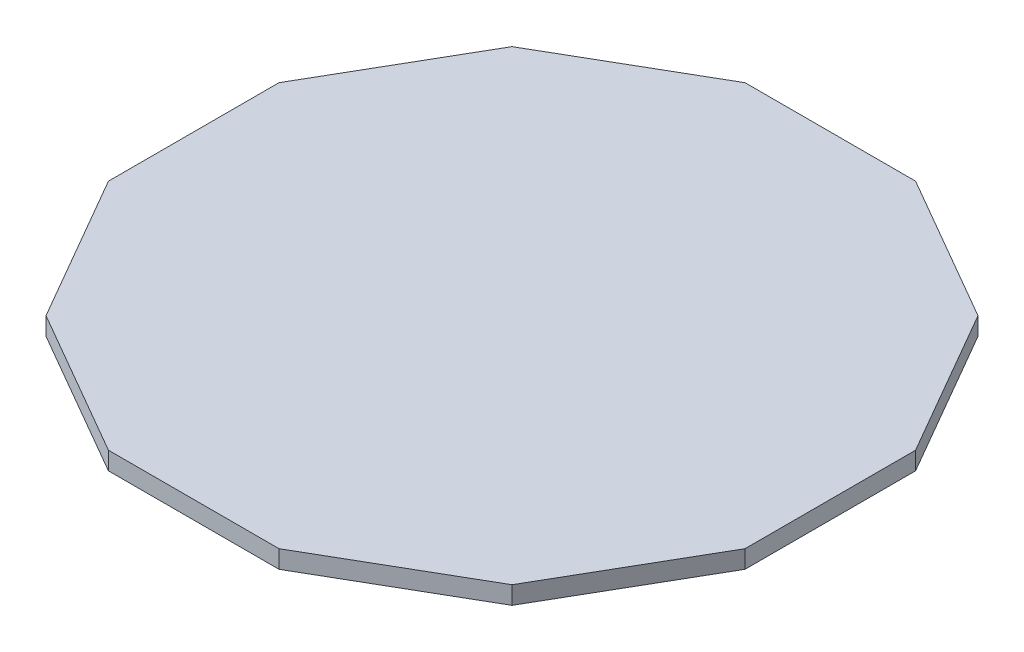
SolidWorks part; units mm, degrees
ref_plane "Front Plane" through (0, 0, 0) normal (0, 0, 1) x (1, 0, 0)
ref_plane "Top Plane" through (0, 0, 0) normal (0, 1, 0) x (1, 0, 0)
ref_plane "Right Plane" through (0, 0, 0) normal (1, 0, 0) x (0, 0, -1)
sketch "Sketch1" plane through (0, 0, 0) normal (0, 1, 0) x (1, 0, 0)
  line L0 (13.148, 49.069) -> (-13.148, 49.069)
  line L1 (-13.148, 49.069) -> (-35.921, 35.921)
  line L2 (-35.921, 35.921) -> (-49.069, 13.148)
  line L3 (-49.069, 13.148) -> (-49.069, -13.148)
  line L4 (-49.069, -13.148) -> (-35.921, -35.921)
  line L5 (-35.921, -35.921) -> (-13.148, -49.069)
  line L6 (-13.148, -49.069) -> (13.148, -49.069)
  line L7 (13.148, -49.069) -> (35.921, -35.921)
  line L8 (35.921, -35.921) -> (49.069, -13.148)
  line L9 (49.069, -13.148) -> (49.069, 13.148)
  line L10 (49.069, 13.148) -> (35.921, 35.921)
  line L11 (35.921, 35.921) -> (13.148, 49.069)
  circle A0 centre (0, 0) radius 50.8
  dimension "D1" = 101.6
extrude "Boss-Extrude1" add sketch "Sketch1" against normal blind 2.921 contours L10 L11 L0 L1 L2 L3 L4 L5 L6 L7 L8 L9 region at (0, 0, 0)
sketch "Sketch2" plane through (0, 0, 0) normal (0, 1, 0) x (1, 0, 0)
  line L24 (51.99, 13.9307) -> (38.0593, 38.0593)
  line L25 (38.0593, 38.0593) -> (13.9307, 51.99)
  line L26 (13.9307, 51.99) -> (-13.9307, 51.99)
  line L27 (-13.9307, 51.99) -> (-38.0593, 38.0593)
  line L28 (-38.0593, 38.0593) -> (-51.99, 13.9307)
  line L29 (-51.99, 13.9307) -> (-51.99, -13.9307)
  line L30 (-51.99, -13.9307) -> (-38.0593, -38.0593)
  line L31 (-38.0593, -38.0593) -> (-13.9307, -51.99)
  line L32 (-13.9307, -51.99) -> (13.9307, -51.99)
  line L33 (13.9307, -51.99) -> (38.0593, -38.0593)
  line L34 (38.0593, -38.0593) -> (51.99, -13.9307)
  line L35 (51.99, -13.9307) -> (51.99, 13.9307)
  line L36 (51.99, 13.9307) -> (38.0593, 38.0593)
  line L37 (38.0593, 38.0593) -> (13.9307, 51.99)
  line L38 (13.9307, 51.99) -> (-13.9307, 51.99)
  line L39 (-13.9307, 51.99) -> (-38.0593, 38.0593)
  line L40 (-38.0593, 38.0593) -> (-51.99, 13.9307)
  line L41 (-51.99, 13.9307) -> (-51.99, -13.9307)
  line L42 (-51.99, -13.9307) -> (-38.0593, -38.0593)
  line L43 (-38.0593, -38.0593) -> (-13.9307, -51.99)
  line L44 (-13.9307, -51.99) -> (13.9307, -51.99)
  line L45 (13.9307, -51.99) -> (38.0593, -38.0593)
  line L46 (38.0593, -38.0593) -> (51.99, -13.9307)
  line L47 (51.99, -13.9307) -> (51.99, 13.9307)
  line L60 (49.069, 13.148) -> (35.921, 35.921)
  line L61 (35.921, 35.921) -> (13.148, 49.069)
  line L62 (13.148, 49.069) -> (-13.148, 49.069)
  line L63 (-13.148, 49.069) -> (-35.921, 35.921)
  line L64 (-35.921, 35.921) -> (-49.069, 13.148)
  line L65 (-49.069, 13.148) -> (-49.069, -13.148)
  line L66 (-49.069, -13.148) -> (-35.921, -35.921)
  line L67 (-35.921, -35.921) -> (-13.148, -49.069)
  line L68 (-13.148, -49.069) -> (13.148, -49.069)
  line L69 (13.148, -49.069) -> (35.921, -35.921)
  line L70 (35.921, -35.921) -> (49.069, -13.148)
  line L71 (49.069, -13.148) -> (49.069, 13.148)
  line L72 (49.069, 13.148) -> (35.921, 35.921)
  line L73 (35.921, 35.921) -> (13.148, 49.069)
  line L74 (13.148, 49.069) -> (-13.148, 49.069)
  line L75 (-13.148, 49.069) -> (-35.921, 35.921)
  line L76 (-35.921, 35.921) -> (-49.069, 13.148)
  line L77 (-49.069, 13.148) -> (-49.069, -13.148)
  line L78 (-49.069, -13.148) -> (-35.921, -35.921)
  line L79 (-35.921, -35.921) -> (-13.148, -49.069)
  line L80 (-13.148, -49.069) -> (13.148, -49.069)
  line L81 (13.148, -49.069) -> (35.921, -35.921)
  line L82 (35.921, -35.921) -> (49.069, -13.148)
  line L83 (49.069, -13.148) -> (49.069, 13.148)
  dimension "D1" = 2.921
  dimension "D2" = 0
extrude "Boss-Extrude2" add sketch "Sketch2" against normal up to surface (2.921 mm away) up to face at (0, -2.921, 0)
